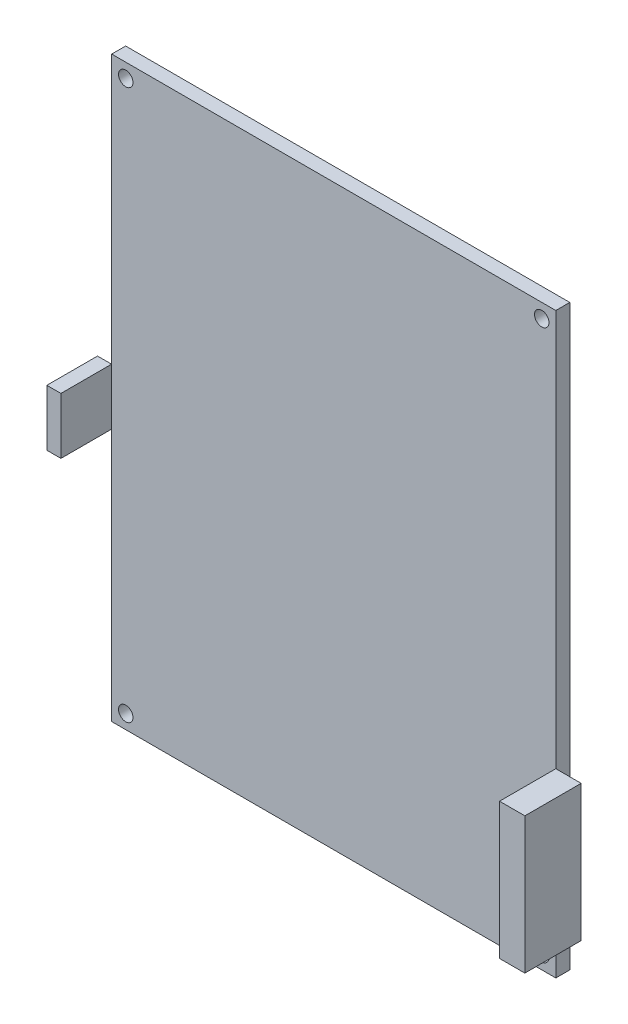
SolidWorks part; units mm, degrees
material "Printed Circuit Board"
ref_plane "Front Plane" through (0, 0, 0) normal (0, 0, 1) x (1, 0, 0)
ref_plane "Top Plane" through (0, 0, 0) normal (0, 1, 0) x (1, 0, 0)
ref_plane "Right Plane" through (0, 0, 0) normal (1, 0, 0) x (0, 0, -1)
sketch "Sketch1" plane through (0, 0, 0) normal (0, 0, 1) x (1, 0, 0)
  line L1 (-50.1015, -65.2145) -> (50.1015, -65.2145)
  line L2 (-50.1015, -65.2145) -> (-50.1015, 65.2145)
  line L3 (-50.1015, 65.2145) -> (50.1015, 65.2145)
  line L4 (50.1015, -65.2145) -> (50.1015, 65.2145)
  line L5 (-50.1015, -65.2145) -> (50.1015, 65.2145) construction
  line L6 (-50.1015, 65.2145) -> (50.1015, -65.2145) construction
  point P0 (0, 0)
  dimension "D1" = 100.203
  dimension "D2" = 130.429
extrude "Extrude1" add sketch "Sketch1" along normal blind 3.1496
sketch "Sketch3" plane through (-50.1015, 0, 0) normal (-1, 0, 0) x (0, 0, 1)
  line L0 (3.1496, -65.2145) -> (0, -65.2145) construction
  line L1 (3.175, 4.6355) -> (14.605, 4.6355)
  line L2 (3.175, 4.6355) -> (3.175, -8.0645)
  line L3 (3.175, -8.0645) -> (14.605, -8.0645)
  line L4 (14.605, 4.6355) -> (14.605, -8.0645)
  line L5 (0, 65.2145) -> (0, -65.2145) construction
  dimension "D1" = 12.7
  dimension "D2" = 11.43
  dimension "D3" = 57.15
  dimension "D4" = 3.175
extrude "Extrude3" add sketch "Sketch3" along normal blind 3.175
sketch "Sketch6" plane through (50.1015, 0, 0) normal (1, 0, 0) x (0, 0, -1)
  line L0 (-3.1496, -65.2145) -> (-3.1496, 65.2145) construction
  line L1 (-3.1496, -55.0545) -> (-15.8496, -55.0545)
  line L2 (-3.1496, -55.0545) -> (-3.1496, -24.3205)
  line L3 (-3.1496, -24.3205) -> (-15.8496, -24.3205)
  line L4 (-15.8496, -55.0545) -> (-15.8496, -24.3205)
  line L5 (-3.1496, -65.2145) -> (0, -65.2145) construction
  dimension "D1" = 30.734
  dimension "D2" = 12.7
  dimension "D3" = 10.16
extrude "Extrude4" add sketch "Sketch6" along normal blind 5.715 separate body
sketch "Sketch4" plane through (0, 0, 3.1496) normal (0, 0, 1) x (1, 0, 0)
  line L0 (-46.9265, 65.2145) -> (-46.9265, 62.0395) construction
  line L1 (50.1015, 65.2145) -> (-50.1015, 65.2145) construction
  line L2 (-46.9265, 62.0395) -> (-50.1015, 62.0395) construction
  line L3 (-50.1015, 65.2145) -> (-50.1015, -65.2145) construction
  line L4 (-50.1015, -62.0395) -> (-46.9265, -62.0395) construction
  line L5 (-46.9265, -62.0395) -> (-46.9265, -65.2145) construction
  line L6 (-50.1015, -65.2145) -> (50.1015, -65.2145) construction
  dimension "D1" = 3.175
hole_wizard "#4 Clearance Hole1" positions "3DSketch1" profile "Sketch5" hole size "#4" standard "Ansi Inch" end condition through all
sketch3d "3DSketch1"
  point P0 (-46.9265, 62.0395, 3.1496)
  point P3 (-46.9265, -62.0395, 3.1496)
sketch "Sketch5" plane through (-46.9265, 62.0395, 3.1496) normal (1, 0, 0) x (0, -1, 0)
  line L0 (0, 0) -> (0, 3.1496)
  line L1 (0, 3.1496) -> (1.6319, 3.1496)
  line L2 (1.6319, 3.1496) -> (1.6319, 0)
  line L5 (1.6319, 0) -> (0, 0)
  line L11 (0, -6.35) -> (0, 107.95) construction
  dimension "Thru Hole Dia." = 3.2639
  dimension "Thru Hole Depth" = 3.1496
mirror "Mirror1" about plane through (0, 0, 0) normal (1, 0, 0) of "#4 Clearance Hole1"
